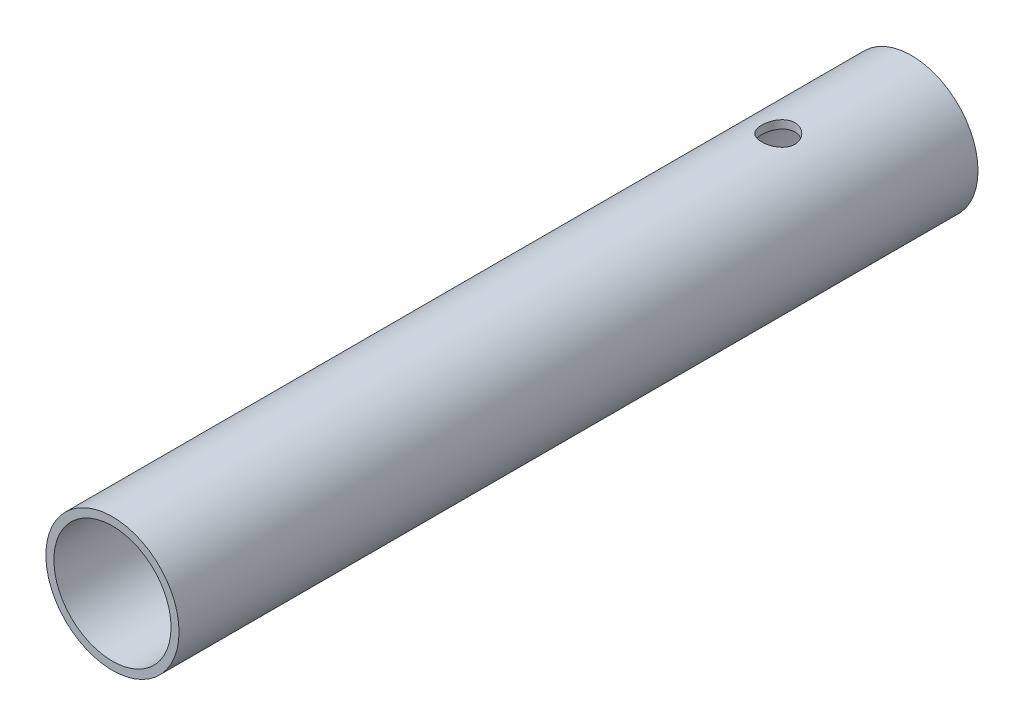
SolidWorks part; units mm, degrees
ref_plane "Front Plane" through (0, 0, 0) normal (0, 0, 1) x (1, 0, 0)
ref_plane "Top Plane" through (0, 0, 0) normal (0, 1, 0) x (1, 0, 0)
ref_plane "Right Plane" through (0, 0, 0) normal (1, 0, 0) x (0, 0, -1)
sketch "Sketch1" plane through (0, 0, 0) normal (0, 0, 1) x (1, 0, 0)
  circle A0 centre (0, 0) radius 25.4 construction
  circle A1 centre (0, 0) radius 22.352 construction
  point P3 (-25.4, 0)
  point P4 (25.4, 0)
  point P6 (-22.352, 0)
  point P7 (22.352, 0)
  dimension "OD" = 50.8
  dimension "Wall" = 3.048
  dimension "ID" = 44.704
sketch "Sketch2" plane through (0, 0, 0) normal (1, 0, 0) x (0, 0, -1)
  line L0 (152.4, 0) -> (-152.4, 0) construction
  line L2 (0, 25.4) -> (0, -25.4) construction
  line L3 (0, 25.4) -> (0, -25.4) construction
  line L4 (152.4, 25.4) -> (-152.4, 25.4) construction
  line L5 (152.4, -25.4) -> (-152.4, -25.4) construction
  line L6 (-152.4, -25.4) -> (-152.4, 25.4) construction
  line L7 (152.4, -25.4) -> (152.4, 25.4) construction
  line L8 (-101.6, -25.4) -> (-101.6, 25.4) construction
  line L9 (101.6, -25.4) -> (101.6, 25.4) construction
  point P3 (0, 0)
  point P9 (0, 25.4)
  point P11 (0, -25.4)
  point P13 (-152.4, 0)
  point P14 (152.4, 25.4)
  point P15 (-152.4, -25.4)
  point P16 (-152.4, 25.4)
  point P17 (-152.4, 0)
  point P18 (152.4, -25.4)
  point P19 (152.4, 0)
  point P22 (-101.6, 0)
  point P25 (101.6, 0)
  point P26 (-101.6, -25.4)
  point P27 (-101.6, 25.4)
  point P28 (101.6, 25.4)
  point P29 (101.6, -25.4)
  dimension "Length" = 304.8
  dimension "D1" = 50.8
sketch "Sketch3" plane through (0, 0, 0) normal (0, 0, 1) x (1, 0, 0)
  circle A0 centre (0, 0) radius 25.4 construction
  circle A1 centre (0, 0) radius 22.352 construction
  circle A2 centre (0, 0) radius 25.4
  circle A3 centre (0, 0) radius 22.352
extrude "Boss-Extrude1" add sketch "Sketch3" along normal mid plane 304.8
ref_plane "Plane1" through (0, 25.4, 0) normal (0, 1, 0) x (1, 0, 0)
sketch "Sketch4" plane through (0, 25.4, 0) normal (0, 1, 0) x (1, 0, 0)
  line L0 (25.4, 152.4) -> (-25.4, 152.4) construction
  line L1 (25.4, -152.4) -> (25.4, 152.4) construction
  circle A0 centre (0, 101.6) radius 6.35
  dimension "D1" = 12.7
  dimension "D2" = 50.8
  dimension "D3" = 25.4
extrude "Cut-Extrude1" cut sketch "Sketch4" against normal through all
equation "\"D1@Sketch2\"=\"OD@Sketch1\""
equation "\"D1@Boss-Extrude1\"=\"Length@Sketch2\""
